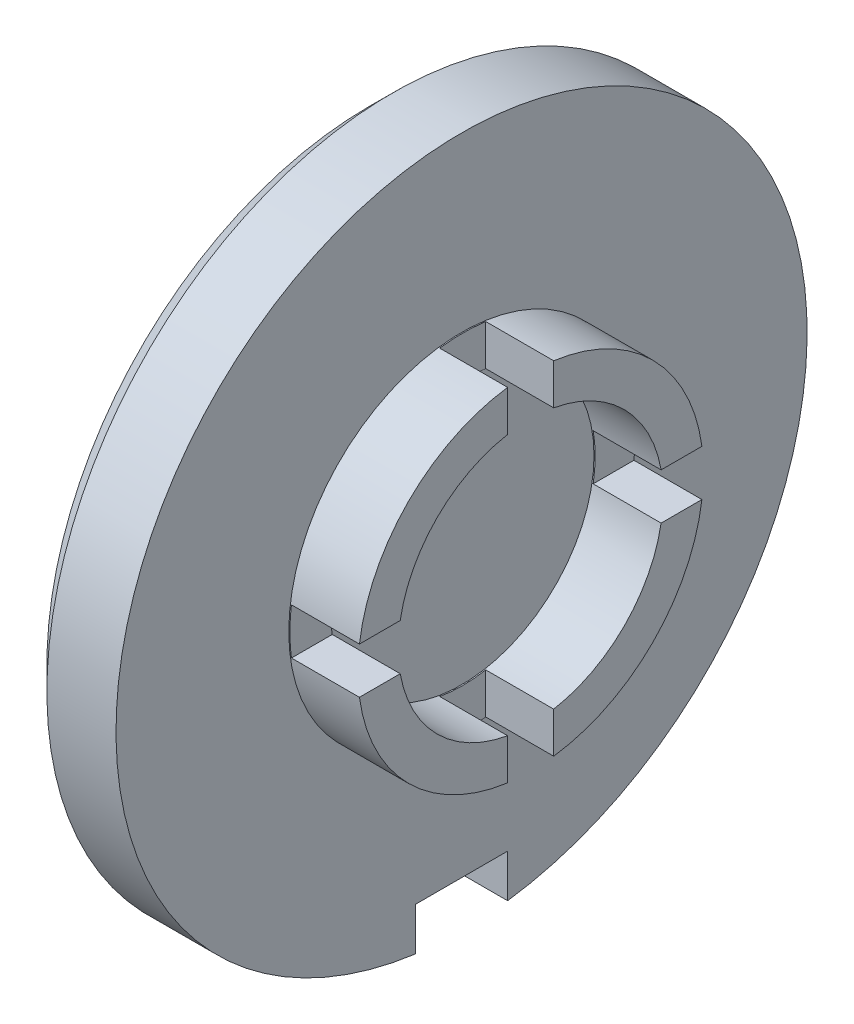
SolidWorks part; units mm, degrees
ref_plane "Front Plane" through (0, 0, 0) normal (0, 0, 1) x (1, 0, 0)
ref_plane "Top Plane" through (0, 0, 0) normal (0, 1, 0) x (1, 0, 0)
ref_plane "Right Plane" through (0, 0, 0) normal (1, 0, 0) x (0, 0, -1)
ref_plane "Plane1" through (0, 0, 66) normal (0, 0, 1) x (1, 0, 0)
sketch "Sketch1" plane through (0, 0, 66) normal (0, 0, 1) x (1, 0, 0)
  line L0 (-81.8, -20) -> (-69, -20) construction
  line L1 (-74, -17.7) -> (-75.2, -17.7)
  line L2 (-75.2, -17.7) -> (-75.2, -20)
  line L3 (-75.2, -20) -> (-76.8, -20)
  line L4 (-76.8, -20) -> (-76.8, -14.4)
  line L5 (-76.8, -14.4) -> (-76.4, -14)
  line L6 (-76.4, -14) -> (-75.2, -14)
  line L7 (-75.2, -14) -> (-75.2, -17)
  line L8 (-75.2, -17) -> (-74, -17)
  line L9 (-74, -17) -> (-74, -17.7)
revolve "Revolve1" add sketch "Sketch1" angle 360 about L0
sketch "Sketch2" plane through (0, 0, 0) normal (0, 0, 1) x (1, 0, 0)
  line L1 (-75.18, -20.4) -> (-73.9, -20.4)
  line L2 (-75.18, -20.4) -> (-75.18, -19.6)
  line L3 (-75.18, -19.6) -> (-73.9, -19.6)
  line L4 (-73.9, -20.4) -> (-73.9, -19.6)
extrude "Boss-Extrude1" add sketch "Sketch2" along normal blind 6.4 from offset 62.8 separate body
combine bodies "Combine1" operation type subtract main body 101 bodies to subtract 102
sketch "Sketch3" plane through (0, 0, 0) normal (0, 0, 1) x (1, 0, 0)
  line L1 (-75.18, -23.2) -> (-73.9, -23.2)
  line L2 (-75.18, -23.2) -> (-75.18, -16.8)
  line L3 (-75.18, -16.8) -> (-73.9, -16.8)
  line L4 (-73.9, -23.2) -> (-73.9, -16.8)
extrude "Boss-Extrude2" add sketch "Sketch3" along normal blind 0.8 from offset 65.6 separate body
combine bodies "Combine2" operation type subtract main body 103 bodies to subtract 104
sketch "Sketch4" plane through (0, 0, 0) normal (0, 0, 1) x (1, 0, 0)
  line L1 (-76.9, -26.1) -> (-75.1, -26.1)
  line L2 (-76.9, -26.1) -> (-76.9, -25.2)
  line L3 (-76.9, -25.2) -> (-75.1, -25.2)
  line L4 (-75.1, -26.1) -> (-75.1, -25.2)
extrude "Boss-Extrude3" add sketch "Sketch4" along normal blind 1.6 from offset 65.2 separate body
combine bodies "Combine3" operation type subtract main body 105 bodies to subtract 106
